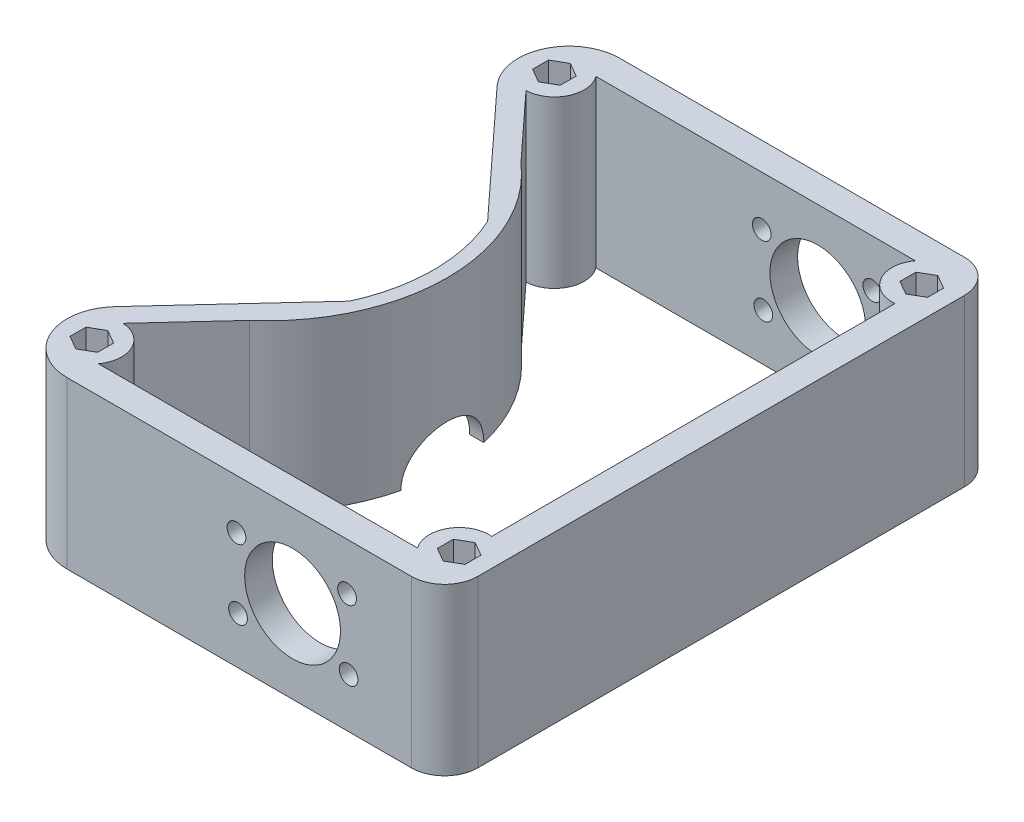
SolidWorks part; units mm, degrees
material "TPU"
ref_plane "Front Plane" through (0, 0, 0) normal (0, 0, 1) x (1, 0, 0)
ref_plane "Top Plane" through (0, 0, 0) normal (0, 1, 0) x (1, 0, 0)
ref_plane "Right Plane" through (0, 0, 0) normal (1, 0, 0) x (0, 0, -1)
sketch "Sketch1" plane through (0, 0, 0) normal (0, 1, 0) x (1, 0, 0)
  line L0 (66.675, 17.145) -> (66.675, 128.905) construction
  line L1 (-28.575, 9.525) -> (66.675, 9.525)
  line L2 (-28.575, 9.525) -> (-28.575, 15.875)
  line L3 (-28.575, 15.875) -> (66.675, 15.875)
  line L4 (66.675, 9.525) -> (66.675, 15.875)
  line L5 (-28.575, 9.525) -> (66.675, 15.875) construction
  line L6 (-28.575, 15.875) -> (66.675, 9.525) construction
  line L9 (-28.575, 9.525) -> (59.055, 9.525) construction
  point P0 (19.05, 12.7)
  point P15 (19.05, 9.525)
  dimension "D1" = 95.25
  dimension "D2" = 6.35
extrude "Boss-Extrude1" add sketch "Sketch1" along normal blind 38.1
sketch "Sketch2" plane through (0, 38.1, 0) normal (0, 1, 0) x (1, 0, 0)
  line L1 (60.325, 9.525) -> (66.675, 9.525)
  line L2 (60.325, 9.525) -> (60.325, 136.525)
  line L3 (60.325, 136.525) -> (66.675, 136.525)
  line L4 (66.675, 9.525) -> (66.675, 136.525)
  line L6 (32.8756, 15.875) -> (32.8756, 130.175) construction
  line L7 (-20.4, 15.875) -> (58.5, 15.875) construction
  line L8 (58.5, 130.175) -> (-20.4, 130.175) construction
  dimension "D1" = 127
  dimension "D2" = 6.35
extrude "Boss-Extrude2" add sketch "Sketch2" against normal up to surface (38.1 mm away) up to face at (19.05, 0, -12.7)
sketch "Sketch3" plane through (0, 38.1, 0) normal (0, 1, 0) x (1, 0, 0)
  line L0 (-28.575, 15.875) -> (-28.575, 9.525) construction
  line L1 (60.325, 136.525) -> (-28.575, 136.525)
  line L2 (60.325, 136.525) -> (60.325, 130.175)
  line L3 (60.325, 130.175) -> (-28.575, 130.175)
  line L4 (-28.575, 136.525) -> (-28.575, 130.175)
extrude "Boss-Extrude3" add sketch "Sketch3" against normal up to surface (38.1 mm away) up to face at (32.8083, 0, -53.975)
sketch "Sketch4" plane through (0, 0, -136.525) normal (0, 0, -1) x (-1, 0, 0)
  line L0 (3.175, 38.1) -> (-66.675, 38.1) construction
  line L1 (-66.675, 19.05) -> (3.175, 19.05) construction
  line L2 (-66.675, 0) -> (-66.675, 38.1) construction
  line L5 (28.575, 19.05) -> (3.175, 19.05) construction
  line L6 (28.575, 0) -> (28.575, 38.1) construction
  circle A0 centre (-31.75, 19.05) radius 11
  point P7 (-31.75, 38.1)
  dimension "D1" = 22
  dimension "D2" = 25.4
extrude "Cut-Extrude1" cut sketch "Sketch4" against normal through all contours A0
sketch "Sketch5" plane through (0, 0, -136.525) normal (0, 0, -1) x (-1, 0, 0)
  circle A0 centre (-18.8777, 26.7049) radius 2.1527
  circle A1 centre (-19.2285, 10.8337) radius 2.1527
  circle A2 centre (-44.6223, 11.3951) radius 2.1527
  circle A3 centre (-44.2715, 27.2663) radius 2.1526
  circle A4 centre (-44.6223, 11.3951) radius 2.1527 construction
  circle A5 centre (-18.8777, 26.7049) radius 2.1526 construction
  circle A6 centre (-19.2285, 10.8337) radius 2.1527 construction
  circle A9 centre (-44.2715, 27.2663) radius 2.1526 construction
extrude "Cut-Extrude2" cut sketch "Sketch5" against normal through all
fillet "Fillet1" radius 7.62 2 edges at (66.675, 19.05, -9.525) (66.675, 19.05, -136.525)
sketch "Sketch10" plane through (0, 38.1, 0) normal (0, 1, 0) x (1, 0, 0)
  line L0 (-28.575, 9.525) -> (59.055, 9.525) construction
  line L2 (-28.575, 15.875) -> (-28.575, 9.525)
  line L5 (66.675, 73.025) -> (-141.5874, 73.025) construction
  line L7 (-28.575, 136.525) -> (-31.75, 136.525)
  line L11 (-31.75, 25.781) -> (-2.821, 57.15)
  line L15 (-28.575, 15.875) -> (-28.575, 22.225)
  line L16 (-28.575, 22.225) -> (-10.4944, 41.8306)
  line L17 (-28.575, 123.825) -> (-10.4944, 104.2194)
  line L18 (-31.75, 120.269) -> (-2.821, 88.9)
  line L19 (-10.4944, 41.8306) -> (-2.821, 57.15) construction
  line L22 (-28.575, 136.525) -> (-28.575, 123.825)
  line L26 (-31.75, 136.525) -> (-31.75, 120.269)
  line L27 (-31.75, 25.781) -> (-31.75, 9.525)
  line L28 (-31.75, 9.525) -> (-28.575, 9.525)
  line L29 (66.675, 17.145) -> (66.675, 128.905) construction
  arc A0 (-2.821, 57.15) -> (-2.821, 88.9) centre (-37.4562, 73.025) ccw
  arc A2 (-10.4944, 104.2194) -> (-10.4944, 41.8306) centre (-37.4562, 73.025) cw
  dimension "D7" = 31.75
  dimension "D6" = 38.1
  dimension "D1" = 16.256
  dimension "D2" = 3.175
  dimension "D3" = 12.7
  dimension "D4" = 42.672
  dimension "D5" = 26.67
extrude "Boss-Extrude4" add sketch "Sketch10" against normal up to surface (38.1 mm away) up to face at (26.0966, 0, -73.025)
sketch "Sketch12" plane through (60.325, 0, 0) normal (-1, 0, 0) x (0, 0, 1)
  line L0 (-88.9, 0) -> (-82.55, 0) construction
  line L1 (-88.9, 0) -> (-57.15, 0) construction
  line L2 (-57.15, 0) -> (-63.5, 0) construction
  line L3 (-82.55, 0) -> (-63.5, 0)
  arc A0 (-82.55, 0) -> (-63.5, 0) centre (-73.025, 0) cw
  dimension "D1" = 19.05
extrude "Cut-Extrude8" cut sketch "Sketch12" along normal up to surface (92.075 mm away) up to face at (-31.75, 19.05, -128.397)
fillet "Fillet2" radius 11.6889 4 edges at (-31.75, 38.1, -128.397) (-31.75, 19.05, -136.525) (-31.75, 0, -128.397) (-31.75, 19.05, -120.269)
fillet "Fillet3" radius 11.6889 4 edges at (-31.75, 38.1, -17.653) (-31.75, 19.05, -25.781) (-31.75, 0, -17.653) (-31.75, 19.05, -9.525)
fillet "Fillet4" radius 6.35 2 edges at (60.325, 19.05, -130.175) (60.325, 19.05, -15.875)
sketch "Sketch15" plane through (0, 38.1, 0) normal (0, 1, 0) x (1, 0, 0)
  line L0 (0.6438, 73.025) -> (66.675, 73.025) construction
  line L1 (66.675, 17.145) -> (66.675, 128.905) construction
  line L2 (-24.7273, 23.5658) -> (-24.7273, 26.7408) construction
  line L3 (-21.5523, 21.7327) -> (-24.7273, 23.5658)
  line L4 (-24.7273, 23.5658) -> (-27.9023, 21.7327)
  line L5 (-27.9023, 21.7327) -> (-27.9023, 18.0665)
  line L6 (-27.9023, 18.0665) -> (-24.7273, 16.2334)
  line L7 (-24.7273, 16.2334) -> (-21.5523, 18.0665)
  line L8 (-21.5523, 18.0665) -> (-21.5523, 21.7327)
  line L9 (-30.7676, 16.5233) -> (63.5, 69.215) construction
  line L10 (63.5, 69.215) -> (63.5, 9.525) construction
  line L11 (59.6523, 129.8166) -> (56.4773, 127.9835)
  line L12 (59.055, 9.525) -> (63.5, 9.525) construction
  line L13 (60.325, 69.215) -> (66.675, 69.215) construction
  line L14 (60.325, 123.825) -> (60.325, 22.225) construction
  line L15 (-21.5523, 127.9835) -> (-21.5523, 124.3173)
  line L16 (-24.7273, 129.8166) -> (-21.5523, 127.9835)
  line L17 (-27.9023, 127.9835) -> (-24.7273, 129.8166)
  line L18 (-27.9023, 124.3173) -> (-27.9023, 127.9835)
  line L19 (-24.7273, 122.4842) -> (-27.9023, 124.3173)
  line L20 (-21.5523, 124.3173) -> (-24.7273, 122.4842)
  line L21 (17.4625, 120.6024) -> (17.4625, 25.4476) construction
  line L22 (62.8273, 127.9835) -> (59.6523, 129.8166)
  line L23 (62.8273, 124.3173) -> (62.8273, 127.9835)
  line L24 (-31.75, 124.8361) -> (-31.75, 21.2139) construction
  line L25 (-31.75, 73.025) -> (66.675, 73.025) construction
  line L26 (59.6523, 122.4842) -> (62.8273, 124.3173)
  line L27 (56.4773, 124.3173) -> (59.6523, 122.4842)
  line L28 (56.4773, 127.9835) -> (56.4773, 124.3173)
  line L29 (56.4773, 18.0665) -> (56.4773, 21.7327)
  line L30 (59.6523, 16.2334) -> (56.4773, 18.0665)
  line L31 (62.8273, 18.0665) -> (59.6523, 16.2334)
  line L32 (62.8273, 21.7327) -> (62.8273, 18.0665)
  line L33 (59.6523, 23.5658) -> (62.8273, 21.7327)
  line L34 (56.4773, 21.7327) -> (59.6523, 23.5658)
  arc A2 (-26.3148, 17.15) -> (-23.1398, 17.15) centre (-24.7273, 19.8996) ccw construction
  circle A3 centre (59.6523, 126.1504) radius 6.8412
  arc A4 (-2.821, 57.15) -> (-2.821, 88.9) centre (-37.4562, 73.025) ccw construction
  circle A7 centre (-24.7273, 19.8996) radius 6.8412
  arc A8 (-28.6538, 29.1383) -> (-20.0611, 9.525) centre (-20.0611, 21.2139) ccw construction
  circle A9 centre (-24.7273, 19.8996) radius 3.175 construction
  circle A10 centre (-24.7273, 126.1504) radius 6.8412
  arc A11 (-20.0611, 136.525) -> (-28.6538, 116.9117) centre (-20.0611, 124.8361) ccw construction
  circle A12 centre (59.6523, 19.8996) radius 6.8412
  point P49 (17.4625, 73.025)
  line M11 (60.325, 123.825) -> (60.325, 22.225)
  arc M12 (60.325, 22.225) -> (53.975, 15.875) centre (53.975, 22.225) cw
  line M13 (53.975, 15.875) -> (-28.575, 15.875)
  line M15 (-28.575, 22.225) -> (-10.4944, 41.8306)
  line M17 (-10.4944, 104.2194) -> (-28.575, 123.825)
  line M19 (-28.575, 130.175) -> (53.975, 130.175)
  arc M20 (53.975, 130.175) -> (60.325, 123.825) centre (53.975, 123.825) cw
  dimension "D1" = 3.175
  dimension "D2" = 3.81
extrude "Boss-Extrude7" add sketch "Sketch15" against normal up to surface (38.1 mm away) contours A7 L8 L7 L6 L5 L4 L3 M15 M13 | A7 L3 L8 M13 M15 | A12 L29 L34 L33 M13 M12 M11 | A12 L33 L32 L31 L30 L29 M11 M12 M13 | A3 L28 L11 L22 L23 L26 M11 M19 M20 | A3 L26 L27 L28 M19 M11 M20 | A10 L20 L19 L18 L17 L16 L15 M17 M19 | A10 L15 L20 M19 M17 up to face at (10.1062, 0, -73.025)
sketch "Sketch21" plane through (0, 38.1, 0) normal (0, 1, 0) x (1, 0, 0)
  line L0 (60.325, 119.3424) -> (60.325, 26.7076) construction
  line L1 (-21.5523, 21.7327) -> (-24.7273, 23.5658)
  line L2 (-24.7273, 23.5658) -> (-27.9023, 21.7327)
  line L3 (-27.9023, 21.7327) -> (-27.9023, 18.0665)
  line L4 (-27.9023, 18.0665) -> (-24.7273, 16.2334)
  line L5 (-24.7273, 16.2334) -> (-21.5523, 18.0665)
  line L6 (-21.5523, 18.0665) -> (-21.5523, 21.7327)
  line L7 (3.7752, 73.025) -> (60.325, 73.025) construction
  line L9 (17.4625, 120.6024) -> (17.4625, 25.4476) construction
  line L10 (56.4773, 18.0665) -> (56.4773, 21.7327)
  line L11 (59.6523, 16.2334) -> (56.4773, 18.0665)
  line L12 (62.8273, 18.0665) -> (59.6523, 16.2334)
  line L13 (62.8273, 21.7327) -> (62.8273, 18.0665)
  line L14 (59.6523, 23.5658) -> (62.8273, 21.7327)
  line L15 (56.4773, 21.7327) -> (59.6523, 23.5658)
  line L16 (59.6523, 129.8166) -> (56.4773, 127.9835)
  line L17 (62.8273, 127.9835) -> (59.6523, 129.8166)
  line L18 (62.8273, 124.3173) -> (62.8273, 127.9835)
  line L19 (59.6523, 122.4842) -> (62.8273, 124.3173)
  line L20 (56.4773, 124.3173) -> (59.6523, 122.4842)
  line L21 (56.4773, 127.9835) -> (56.4773, 124.3173)
  line L22 (-21.5523, 127.9835) -> (-21.5523, 124.3173)
  line L23 (-24.7273, 129.8166) -> (-21.5523, 127.9835)
  line L24 (-27.9023, 127.9835) -> (-24.7273, 129.8166)
  line L25 (-27.9023, 124.3173) -> (-27.9023, 127.9835)
  line L26 (-24.7273, 122.4842) -> (-27.9023, 124.3173)
  line L27 (-21.5523, 124.3173) -> (-24.7273, 122.4842)
  circle A0 centre (-24.7273, 19.8996) radius 3.175 construction
  arc A1 (-10.4944, 41.8306) -> (-10.4944, 104.2194) centre (-37.4562, 73.025) ccw construction
extrude "Cut-Extrude12" cut sketch "Sketch21" against normal through all
